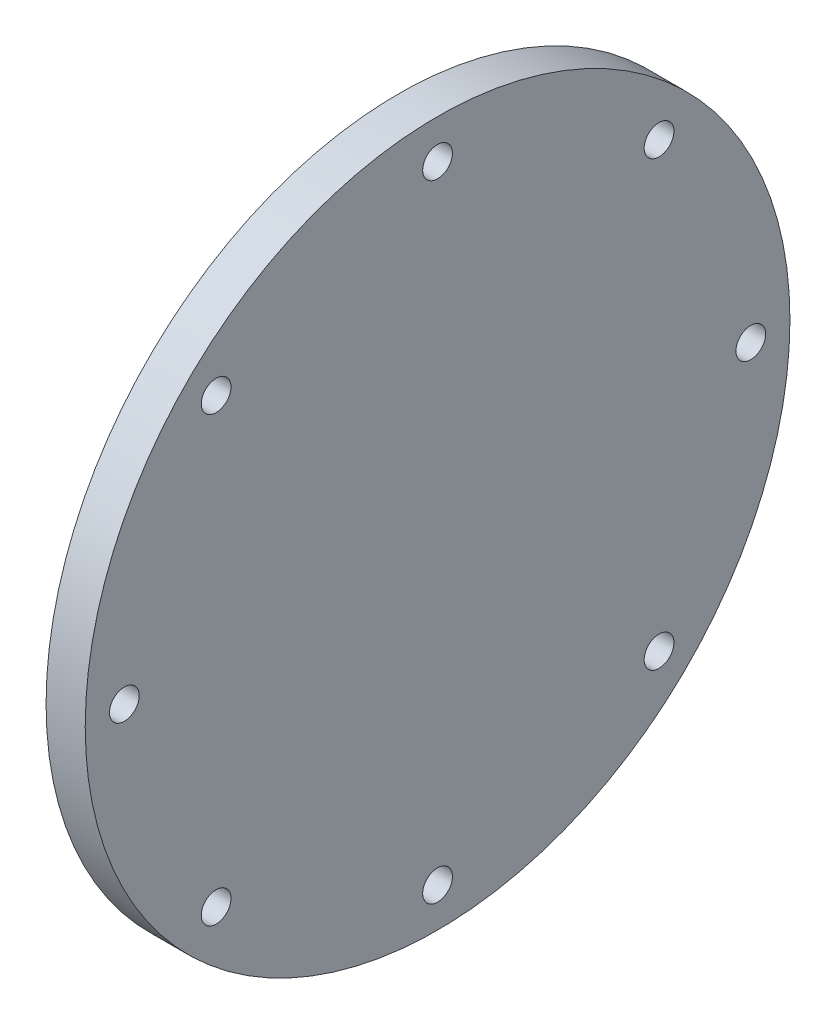
SolidWorks part; units mm, degrees
material "7075-T6 (SN)"
ref_plane "Front Plane" through (0, 0, 0) normal (0, 0, 1) x (1, 0, 0)
ref_plane "Top Plane" through (0, 0, 0) normal (0, 1, 0) x (1, 0, 0)
ref_plane "Right Plane" through (0, 0, 0) normal (1, 0, 0) x (0, 0, -1)
sketch "Sketch1" plane through (0, 0, 0) normal (1, 0, 0) x (0, 0, -1)
  circle A0 centre (0, 0) radius 57.15
  dimension "D1" = 114.3
extrude "Boss-Extrude1" add sketch "Sketch1" along normal blind 6.35
sketch "Sketch2" plane through (0, 0, 0) normal (-1, 0, 0) x (0, 0, 1)
  circle A0 centre (0, 0) radius 45.847
  dimension "D1" = 91.694
extrude "Boss-Extrude2" add sketch "Sketch2" along normal blind 6.35
sketch "Sketch3" plane through (6.35, 0, 0) normal (1, 0, 0) x (0, 0, -1)
  circle A0 centre (0, 0) radius 50.8 construction
  circle A1 centre (0, 50.8) radius 2.413
  circle A2 centre (35.921, 35.921) radius 2.413
  circle A3 centre (50.8, 0) radius 2.413
  circle A4 centre (35.921, -35.921) radius 2.413
  circle A5 centre (0, -50.8) radius 2.413
  circle A6 centre (-35.921, -35.921) radius 2.413
  circle A7 centre (-50.8, 0) radius 2.413
  circle A8 centre (-35.921, 35.921) radius 2.413
  point P21 (0, 0)
  dimension "D1" = 101.6
  dimension "D2" = 4.826
  dimension "D3" = 8
extrude "Cut-Extrude1" cut sketch "Sketch3" against normal through all
